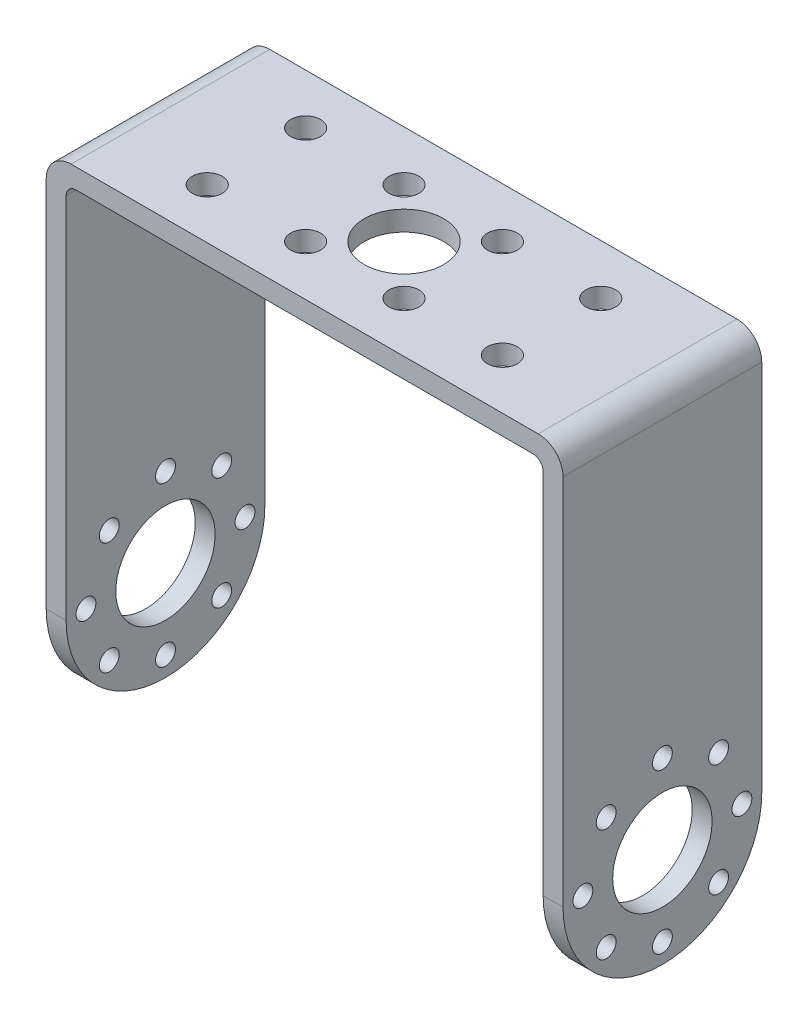
SolidWorks part; units mm, degrees
material "5052-H36"
ref_plane "前视基准面" through (0, 0, 0) normal (0, 0, 1) x (1, 0, 0)
ref_plane "上视基准面" through (0, 0, 0) normal (0, 1, 0) x (1, 0, 0)
ref_plane "右视基准面" through (0, 0, 0) normal (1, 0, 0) x (0, 0, -1)
sketch "草图1" plane through (0, 0, 0) normal (0, 0, 1) x (1, 0, 0)
  line L0 (-24, 23) -> (24, 23)
  line L1 (-26, -25) -> (-24, -25)
  line L2 (-26, -25) -> (-26, 25)
  line L3 (-26, 25) -> (26, 25)
  line L4 (26, -25) -> (26, 25)
  line L5 (-26, -25) -> (26, 25) construction
  line L6 (-26, 25) -> (26, -25) construction
  line L7 (-24, 23) -> (24, 23) construction
  line L8 (24, 23) -> (24, -25)
  line L10 (-24, 23) -> (-24, -25)
  line L11 (24, -25) -> (26, -25)
  point P0 (0, 0)
  dimension "D1" = 52
  dimension "D2" = 50
  dimension "D3" = 2
  dimension "D4" = 2
  dimension "D5" = 2
extrude "凸台-拉伸1" add sketch "草图1" along normal blind 20
fillet "圆角1" radius 10 4 edges at (-25, -25, 20) (-25, -25, 0) (25, -25, 0) (25, -25, 20)
sketch "草图3" plane through (0, 25, 0) normal (0, 1, 0) x (1, 0, 0)
  line L0 (-26, 0) -> (26, -20) construction
  line L1 (-26, -20) -> (26, 0) construction
  line L2 (0, -10) -> (0, 0) construction
  line L3 (0, 0) -> (0, -20) construction
  line L4 (26, -20) -> (-26, -20) construction
  line L5 (0, -20) -> (0, -10) construction
  line L6 (0, -10) -> (-26, -10) construction
  line L7 (-26, -20) -> (-26, 0) construction
  line L8 (-26, -10) -> (26, -10) construction
  line L9 (-4.9497, -14.9497) -> (0, -10) construction
  line L10 (4.9497, -14.9497) -> (-4.9497, -14.9497) construction
  line L11 (-4.9497, -14.9497) -> (-14.8492, -14.9497) construction
  circle A10 centre (0, -10) radius 4
  circle A11 centre (-4.9497, -14.9497) radius 1.5
  circle A12 centre (-4.9497, -5.0503) radius 1.5
  circle A13 centre (4.9497, -5.0503) radius 1.5
  circle A14 centre (4.9497, -14.9497) radius 1.5
  circle A15 centre (-14.8492, -14.9497) radius 1.5
  circle A16 centre (-14.8492, -5.0503) radius 1.5
  circle A17 centre (14.8492, -5.0503) radius 1.5
  circle A18 centre (14.8492, -14.9497) radius 1.5
  point P31 (0, -10)
  dimension "D1" = 8
  dimension "D2" = 3
  dimension "D3" = 7
  dimension "D4" = 45
  dimension "D6" = 2
  dimension "D5" = 4
extrude "切除-拉伸1" cut sketch "草图3" against normal up to next
sketch "草图4" plane through (-26, 0, 0) normal (-1, 0, 0) x (0, 0, 1)
  line L0 (0, -15) -> (20, -15) construction
  line L1 (0, 25) -> (0, -15) construction
  line L2 (20, 25) -> (20, -15) construction
  line L3 (10, -25) -> (10, -15) construction
  line L4 (10, -15) -> (15.3917, -9.6083) construction
  line L6 (10, -15) -> (14.9497, -3.3003) construction
  circle A0 centre (10, -15) radius 5
  circle A3 centre (10, -7) radius 1
  circle A4 centre (15.6569, -9.3431) radius 1
  circle A5 centre (18, -15) radius 1
  circle A6 centre (15.6569, -20.6569) radius 1
  circle A7 centre (10, -23) radius 1
  circle A8 centre (4.3431, -20.6569) radius 1
  circle A9 centre (2, -15) radius 1
  circle A10 centre (4.3431, -9.3431) radius 1
  point P30 (10, -15)
  dimension "D2" = 8
  dimension "D6" = 10
  dimension "D7" = 2
  dimension "D1" = 10
  dimension "D3" = 45
  dimension "D4" = 8
extrude "切除-拉伸2" cut sketch "草图4" against normal through all
fillet "圆角2" radius 2.5 2 edges at (-26, 25, 10) (26, 25, 10)
fillet "圆角3" radius 1 2 edges at (-24, 23, 10) (24, 23, 10)
